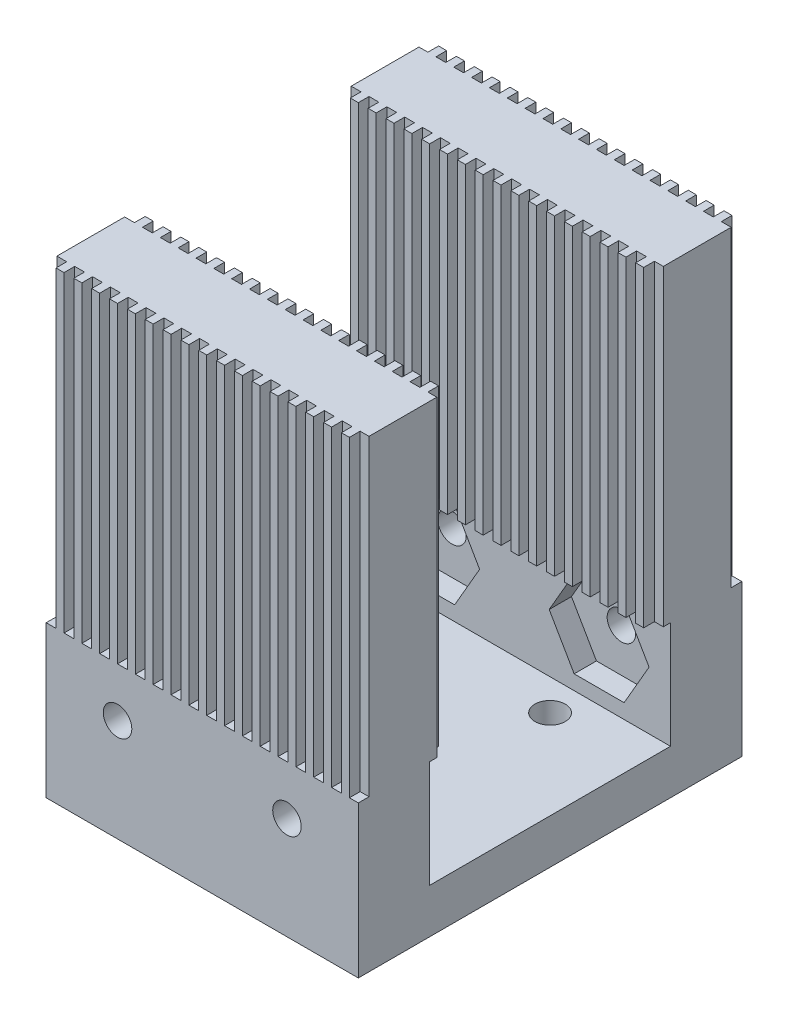
SolidWorks part; units mm, degrees
ref_plane "Front Plane" through (0, 0, 0) normal (0, 0, 1) x (1, 0, 0)
ref_plane "Top Plane" through (0, 0, 0) normal (0, 1, 0) x (1, 0, 0)
ref_plane "Right Plane" through (0, 0, 0) normal (1, 0, 0) x (0, 0, -1)
sketch "Sketch11" plane through (0, 0, 12.5) normal (0, -1, 0) x (1, 0, 0)
  line L1 (0, 0) -> (35, 0)
  line L2 (0, 0) -> (0, -27)
  line L3 (0, -27) -> (35, -27)
  line L4 (35, 0) -> (35, -27)
  dimension "D1" = 27
  dimension "D2" = 35
extrude "Boss-Extrude6" add sketch "Sketch11" along normal blind 5
sketch "Sketch12" plane through (0, -5, 0) normal (0, -1, 0) x (1, 0, 0)
  line L0 (0, 12.5) -> (0, -14.5) construction
  line L1 (0, -14.5) -> (35, -14.5) construction
  line L3 (35, 12.5) -> (0, 12.5) construction
  circle A0 centre (10, 9) radius 1.7
  circle A1 centre (25, 9) radius 1.7
  circle A2 centre (25, -11) radius 1.7
  circle A3 centre (10, -11) radius 1.7
  point P0 (17.5, -1)
  dimension "D3" = 3.4
  dimension "D4" = 7.5
  dimension "D1" = 17.5
  dimension "D2" = 13.5
  dimension "D5" = 10
  dimension "D7" = 27
  dimension "D6" = 2
extrude "Cut-Extrude3" cut sketch "Sketch12" against normal blind 5
sketch "Sketch13" plane through (0, -5, 0) normal (0, -1, 0) x (1, 0, 0)
  line L1 (35, -14.5) -> (0, -14.5)
  line L2 (35, -14.5) -> (35, -22.5)
  line L3 (35, -22.5) -> (0, -22.5)
  line L4 (0, -14.5) -> (0, -22.5)
  line L5 (35, 12.5) -> (0, 12.5)
  line L6 (35, 12.5) -> (35, 20.5)
  line L7 (35, 20.5) -> (0, 20.5)
  line L8 (0, 12.5) -> (0, 20.5)
  dimension "D1" = 8
  dimension "D2" = 8
extrude "Boss-Extrude7" add sketch "Sketch13" against normal blind 17
sketch "Sketch14" plane through (0, 12, 0) normal (0, 1, 0) x (1, 0, 0)
  line L0 (0, -12.5) -> (35, -12.5) construction
  line L1 (35, -20.5) -> (0, -20.5)
  line L2 (35, -20.5) -> (35, -10.5)
  line L3 (35, -10.5) -> (0, -10.5)
  line L4 (0, -20.5) -> (0, -10.5)
  line L5 (0, 22.5) -> (35, 22.5)
  line L6 (0, 22.5) -> (0, 12.5)
  line L7 (0, 12.5) -> (35, 12.5)
  line L8 (35, 22.5) -> (35, 12.5)
  line L9 (35, 14.5) -> (0, 14.5) construction
  dimension "D1" = 2
  dimension "D2" = 2
extrude "Boss-Extrude8" add sketch "Sketch14" along normal blind 35
sketch "Sketch15" plane through (0, 0, 10.5) normal (0, 0, -1) x (-1, 0, 0)
  line L0 (-35, 47) -> (0, 47) construction
  line L1 (0, 12) -> (-1.1, 12)
  line L2 (0, 12) -> (0, 47)
  line L3 (0, 47) -> (-1.1, 47)
  line L4 (-1.1, 12) -> (-1.1, 47)
  line L5 (-3.1, 12) -> (-3.1, 47)
  line L6 (-2, 47) -> (-3.1, 47)
  line L7 (-2, 12) -> (-2, 47)
  line L8 (-2, 12) -> (-3.1, 12)
  line L9 (-5.1, 12) -> (-5.1, 47)
  line L10 (-4, 47) -> (-5.1, 47)
  line L11 (-4, 12) -> (-4, 47)
  line L12 (-4, 12) -> (-5.1, 12)
  line L13 (-7.1, 12) -> (-7.1, 47)
  line L14 (-6, 47) -> (-7.1, 47)
  line L15 (-6, 12) -> (-6, 47)
  line L16 (-6, 12) -> (-7.1, 12)
  line L17 (-9.1, 12) -> (-9.1, 47)
  line L18 (-8, 47) -> (-9.1, 47)
  line L19 (-8, 12) -> (-8, 47)
  line L20 (-8, 12) -> (-9.1, 12)
  line L21 (-11.1, 12) -> (-11.1, 47)
  line L22 (-10, 47) -> (-11.1, 47)
  line L23 (-10, 12) -> (-10, 47)
  line L24 (-10, 12) -> (-11.1, 12)
  line L25 (-13.1, 12) -> (-13.1, 47)
  line L26 (-12, 47) -> (-13.1, 47)
  line L27 (-12, 12) -> (-12, 47)
  line L28 (-12, 12) -> (-13.1, 12)
  line L29 (-15.1, 12) -> (-15.1, 47)
  line L30 (-14, 47) -> (-15.1, 47)
  line L31 (-14, 12) -> (-14, 47)
  line L32 (-14, 12) -> (-15.1, 12)
  line L33 (-17.1, 12) -> (-17.1, 47)
  line L34 (-16, 47) -> (-17.1, 47)
  line L35 (-16, 12) -> (-16, 47)
  line L36 (-16, 12) -> (-17.1, 12)
  line L37 (-19.1, 12) -> (-19.1, 47)
  line L38 (-18, 47) -> (-19.1, 47)
  line L39 (-18, 12) -> (-18, 47)
  line L40 (-18, 12) -> (-19.1, 12)
  line L41 (-21.1, 12) -> (-21.1, 47)
  line L42 (-20, 47) -> (-21.1, 47)
  line L43 (-20, 12) -> (-20, 47)
  line L44 (-20, 12) -> (-21.1, 12)
  line L45 (-23.1, 12) -> (-23.1, 47)
  line L46 (-22, 47) -> (-23.1, 47)
  line L47 (-22, 12) -> (-22, 47)
  line L48 (-22, 12) -> (-23.1, 12)
  line L49 (-25.1, 12) -> (-25.1, 47)
  line L50 (-24, 47) -> (-25.1, 47)
  line L51 (-24, 12) -> (-24, 47)
  line L52 (-24, 12) -> (-25.1, 12)
  line L53 (-27.1, 12) -> (-27.1, 47)
  line L54 (-26, 47) -> (-27.1, 47)
  line L55 (-26, 12) -> (-26, 47)
  line L56 (-26, 12) -> (-27.1, 12)
  line L57 (-29.1, 12) -> (-29.1, 47)
  line L58 (-28, 47) -> (-29.1, 47)
  line L59 (-28, 12) -> (-28, 47)
  line L60 (-28, 12) -> (-29.1, 12)
  line L61 (-31.1, 12) -> (-31.1, 47)
  line L62 (-30, 47) -> (-31.1, 47)
  line L63 (-30, 12) -> (-30, 47)
  line L64 (-30, 12) -> (-31.1, 12)
  line L65 (-33.1, 12) -> (-33.1, 47)
  line L66 (-32, 47) -> (-33.1, 47)
  line L67 (-32, 12) -> (-32, 47)
  line L68 (-32, 12) -> (-33.1, 12)
  line L69 (-35.1, 12) -> (-35.1, 47)
  line L70 (-34, 47) -> (-35.1, 47)
  line L71 (-34, 12) -> (-34, 47)
  line L72 (-34, 12) -> (-35.1, 12)
  dimension "D1" = 1.1
  dimension "D2" = 18
extrude "Cut-Extrude4" cut sketch "Sketch15" against normal blind 1.2
sketch "Sketch16" plane through (0, 0, -12.5) normal (0, 0, 1) x (1, 0, 0)
  line L0 (0, 12) -> (35, 12) construction
  line L1 (0, 47) -> (1.1, 47)
  line L2 (0, 47) -> (0, 12)
  line L3 (0, 12) -> (1.1, 12)
  line L4 (1.1, 47) -> (1.1, 12)
  line L5 (2, 47) -> (2, 12)
  line L6 (2, 12) -> (3.1, 12)
  line L7 (3.1, 47) -> (3.1, 12)
  line L8 (2, 47) -> (3.1, 47)
  line L9 (4, 47) -> (4, 12)
  line L10 (4, 12) -> (5.1, 12)
  line L11 (5.1, 47) -> (5.1, 12)
  line L12 (4, 47) -> (5.1, 47)
  line L13 (6, 47) -> (6, 12)
  line L14 (6, 12) -> (7.1, 12)
  line L15 (7.1, 47) -> (7.1, 12)
  line L16 (6, 47) -> (7.1, 47)
  line L17 (8, 47) -> (8, 12)
  line L18 (8, 12) -> (9.1, 12)
  line L19 (9.1, 47) -> (9.1, 12)
  line L20 (8, 47) -> (9.1, 47)
  line L21 (10, 47) -> (10, 12)
  line L22 (10, 12) -> (11.1, 12)
  line L23 (11.1, 47) -> (11.1, 12)
  line L24 (10, 47) -> (11.1, 47)
  line L25 (12, 47) -> (12, 12)
  line L26 (12, 12) -> (13.1, 12)
  line L27 (13.1, 47) -> (13.1, 12)
  line L28 (12, 47) -> (13.1, 47)
  line L29 (14, 47) -> (14, 12)
  line L30 (14, 12) -> (15.1, 12)
  line L31 (15.1, 47) -> (15.1, 12)
  line L32 (14, 47) -> (15.1, 47)
  line L33 (16, 47) -> (16, 12)
  line L34 (16, 12) -> (17.1, 12)
  line L35 (17.1, 47) -> (17.1, 12)
  line L36 (16, 47) -> (17.1, 47)
  line L37 (18, 47) -> (18, 12)
  line L38 (18, 12) -> (19.1, 12)
  line L39 (19.1, 47) -> (19.1, 12)
  line L40 (18, 47) -> (19.1, 47)
  line L41 (20, 47) -> (20, 12)
  line L42 (20, 12) -> (21.1, 12)
  line L43 (21.1, 47) -> (21.1, 12)
  line L44 (20, 47) -> (21.1, 47)
  line L45 (22, 47) -> (22, 12)
  line L46 (22, 12) -> (23.1, 12)
  line L47 (23.1, 47) -> (23.1, 12)
  line L48 (22, 47) -> (23.1, 47)
  line L49 (24, 47) -> (24, 12)
  line L50 (24, 12) -> (25.1, 12)
  line L51 (25.1, 47) -> (25.1, 12)
  line L52 (24, 47) -> (25.1, 47)
  line L53 (26, 47) -> (26, 12)
  line L54 (26, 12) -> (27.1, 12)
  line L55 (27.1, 47) -> (27.1, 12)
  line L56 (26, 47) -> (27.1, 47)
  line L57 (28, 47) -> (28, 12)
  line L58 (28, 12) -> (29.1, 12)
  line L59 (29.1, 47) -> (29.1, 12)
  line L60 (28, 47) -> (29.1, 47)
  line L61 (30, 47) -> (30, 12)
  line L62 (30, 12) -> (31.1, 12)
  line L63 (31.1, 47) -> (31.1, 12)
  line L64 (30, 47) -> (31.1, 47)
  line L65 (32, 47) -> (32, 12)
  line L66 (32, 12) -> (33.1, 12)
  line L67 (33.1, 47) -> (33.1, 12)
  line L68 (32, 47) -> (33.1, 47)
  line L69 (34, 47) -> (34, 12)
  line L70 (34, 12) -> (35.1, 12)
  line L71 (35.1, 47) -> (35.1, 12)
  line L72 (34, 47) -> (35.1, 47)
  dimension "D1" = 1.1
  dimension "D2" = 18
extrude "Cut-Extrude5" cut sketch "Sketch16" against normal blind 1.2
sketch "Sketch17" plane through (0, 0, 20.5) normal (0, 0, 1) x (1, 0, 0)
  line L0 (2, 47) -> (2, 12)
  line L1 (0, 47) -> (1.1, 47)
  line L2 (0, 47) -> (0, 12)
  line L3 (0, 12) -> (1.1, 12)
  line L4 (1.1, 47) -> (1.1, 12)
  line L5 (2, 47) -> (3.1, 47)
  line L6 (3.1, 47) -> (3.1, 12)
  line L7 (2, 12) -> (3.1, 12)
  line L8 (4, 47) -> (4, 12)
  line L9 (4, 47) -> (5.1, 47)
  line L10 (5.1, 47) -> (5.1, 12)
  line L11 (4, 12) -> (5.1, 12)
  line L12 (6, 47) -> (6, 12)
  line L13 (6, 47) -> (7.1, 47)
  line L14 (7.1, 47) -> (7.1, 12)
  line L15 (6, 12) -> (7.1, 12)
  line L16 (8, 47) -> (8, 12)
  line L17 (8, 47) -> (9.1, 47)
  line L18 (9.1, 47) -> (9.1, 12)
  line L19 (8, 12) -> (9.1, 12)
  line L20 (10, 47) -> (10, 12)
  line L21 (10, 47) -> (11.1, 47)
  line L22 (11.1, 47) -> (11.1, 12)
  line L23 (10, 12) -> (11.1, 12)
  line L24 (12, 47) -> (12, 12)
  line L25 (12, 47) -> (13.1, 47)
  line L26 (13.1, 47) -> (13.1, 12)
  line L27 (12, 12) -> (13.1, 12)
  line L28 (14, 47) -> (14, 12)
  line L29 (14, 47) -> (15.1, 47)
  line L30 (15.1, 47) -> (15.1, 12)
  line L31 (14, 12) -> (15.1, 12)
  line L32 (16, 47) -> (16, 12)
  line L33 (16, 47) -> (17.1, 47)
  line L34 (17.1, 47) -> (17.1, 12)
  line L35 (16, 12) -> (17.1, 12)
  line L36 (18, 47) -> (18, 12)
  line L37 (18, 47) -> (19.1, 47)
  line L38 (19.1, 47) -> (19.1, 12)
  line L39 (18, 12) -> (19.1, 12)
  line L40 (20, 47) -> (20, 12)
  line L41 (20, 47) -> (21.1, 47)
  line L42 (21.1, 47) -> (21.1, 12)
  line L43 (20, 12) -> (21.1, 12)
  line L44 (22, 47) -> (22, 12)
  line L45 (22, 47) -> (23.1, 47)
  line L46 (23.1, 47) -> (23.1, 12)
  line L47 (22, 12) -> (23.1, 12)
  line L48 (24, 47) -> (24, 12)
  line L49 (24, 47) -> (25.1, 47)
  line L50 (25.1, 47) -> (25.1, 12)
  line L51 (24, 12) -> (25.1, 12)
  line L52 (26, 47) -> (26, 12)
  line L53 (26, 47) -> (27.1, 47)
  line L54 (27.1, 47) -> (27.1, 12)
  line L55 (26, 12) -> (27.1, 12)
  line L56 (28, 47) -> (28, 12)
  line L57 (28, 47) -> (29.1, 47)
  line L58 (29.1, 47) -> (29.1, 12)
  line L59 (28, 12) -> (29.1, 12)
  line L60 (30, 47) -> (30, 12)
  line L61 (30, 47) -> (31.1, 47)
  line L62 (31.1, 47) -> (31.1, 12)
  line L63 (30, 12) -> (31.1, 12)
  line L64 (32, 47) -> (32, 12)
  line L65 (32, 47) -> (33.1, 47)
  line L66 (33.1, 47) -> (33.1, 12)
  line L67 (32, 12) -> (33.1, 12)
  line L68 (34, 47) -> (34, 12)
  line L69 (34, 47) -> (35.1, 47)
  line L70 (35.1, 47) -> (35.1, 12)
  line L71 (34, 12) -> (35.1, 12)
  dimension "D1" = 1.1
  dimension "D2" = 35
  dimension "D3" = 18
extrude "Cut-Extrude6" cut sketch "Sketch17" against normal blind 1.2
sketch "Sketch18" plane through (0, 0, -22.5) normal (0, 0, -1) x (-1, 0, 0)
  line L0 (-31.9, 47) -> (-31.9, 12)
  line L1 (-35, 47) -> (-33.9, 47)
  line L2 (-35, 47) -> (-35, 12)
  line L3 (-35, 12) -> (-33.9, 12)
  line L4 (-33.9, 47) -> (-33.9, 12)
  line L5 (-33, 12) -> (-31.9, 12)
  line L6 (-33, 47) -> (-33, 12)
  line L7 (-33, 47) -> (-31.9, 47)
  line L8 (-29.9, 47) -> (-29.9, 12)
  line L9 (-31, 12) -> (-29.9, 12)
  line L10 (-31, 47) -> (-31, 12)
  line L11 (-31, 47) -> (-29.9, 47)
  line L12 (-27.9, 47) -> (-27.9, 12)
  line L13 (-29, 12) -> (-27.9, 12)
  line L14 (-29, 47) -> (-29, 12)
  line L15 (-29, 47) -> (-27.9, 47)
  line L16 (-25.9, 47) -> (-25.9, 12)
  line L17 (-27, 12) -> (-25.9, 12)
  line L18 (-27, 47) -> (-27, 12)
  line L19 (-27, 47) -> (-25.9, 47)
  line L20 (-23.9, 47) -> (-23.9, 12)
  line L21 (-25, 12) -> (-23.9, 12)
  line L22 (-25, 47) -> (-25, 12)
  line L23 (-25, 47) -> (-23.9, 47)
  line L24 (-21.9, 47) -> (-21.9, 12)
  line L25 (-23, 12) -> (-21.9, 12)
  line L26 (-23, 47) -> (-23, 12)
  line L27 (-23, 47) -> (-21.9, 47)
  line L28 (-19.9, 47) -> (-19.9, 12)
  line L29 (-21, 12) -> (-19.9, 12)
  line L30 (-21, 47) -> (-21, 12)
  line L31 (-21, 47) -> (-19.9, 47)
  line L32 (-17.9, 47) -> (-17.9, 12)
  line L33 (-19, 12) -> (-17.9, 12)
  line L34 (-19, 47) -> (-19, 12)
  line L35 (-19, 47) -> (-17.9, 47)
  line L36 (-15.9, 47) -> (-15.9, 12)
  line L37 (-17, 12) -> (-15.9, 12)
  line L38 (-17, 47) -> (-17, 12)
  line L39 (-17, 47) -> (-15.9, 47)
  line L40 (-13.9, 47) -> (-13.9, 12)
  line L41 (-15, 12) -> (-13.9, 12)
  line L42 (-15, 47) -> (-15, 12)
  line L43 (-15, 47) -> (-13.9, 47)
  line L44 (-11.9, 47) -> (-11.9, 12)
  line L45 (-13, 12) -> (-11.9, 12)
  line L46 (-13, 47) -> (-13, 12)
  line L47 (-13, 47) -> (-11.9, 47)
  line L48 (-9.9, 47) -> (-9.9, 12)
  line L49 (-11, 12) -> (-9.9, 12)
  line L50 (-11, 47) -> (-11, 12)
  line L51 (-11, 47) -> (-9.9, 47)
  line L52 (-7.9, 47) -> (-7.9, 12)
  line L53 (-9, 12) -> (-7.9, 12)
  line L54 (-9, 47) -> (-9, 12)
  line L55 (-9, 47) -> (-7.9, 47)
  line L56 (-5.9, 47) -> (-5.9, 12)
  line L57 (-7, 12) -> (-5.9, 12)
  line L58 (-7, 47) -> (-7, 12)
  line L59 (-7, 47) -> (-5.9, 47)
  line L60 (-3.9, 47) -> (-3.9, 12)
  line L61 (-5, 12) -> (-3.9, 12)
  line L62 (-5, 47) -> (-5, 12)
  line L63 (-5, 47) -> (-3.9, 47)
  line L64 (-1.9, 47) -> (-1.9, 12)
  line L65 (-3, 12) -> (-1.9, 12)
  line L66 (-3, 47) -> (-3, 12)
  line L67 (-3, 47) -> (-1.9, 47)
  line L68 (0.1, 47) -> (0.1, 12)
  line L69 (-1, 12) -> (0.1, 12)
  line L70 (-1, 47) -> (-1, 12)
  line L71 (-1, 47) -> (0.1, 47)
  dimension "D1" = 1.1
  dimension "D2" = 35
  dimension "D3" = 18
extrude "Cut-Extrude7" cut sketch "Sketch18" against normal blind 1.2
sketch "Sketch19" plane through (0, 0, -22.5) normal (0, 0, -1) x (-1, 0, 0)
  line L0 (-35, 12) -> (-35, -5) construction
  line L1 (0, 12) -> (0, -5) construction
  circle A0 centre (-27, 6.4851) radius 1.6
  circle A1 centre (-8, 6.4851) radius 1.6
  dimension "D1" = 8
  dimension "D2" = 8
extrude "Cut-Extrude8" cut sketch "Sketch19" against normal through all
sketch "Sketch20" plane through (0, 0, -14.5) normal (0, 0, 1) x (1, 0, 0)
  line L1 (29.8, 1.6354) -> (32.6, 6.4851)
  line L2 (32.6, 6.4851) -> (29.8, 11.3348)
  line L3 (29.8, 11.3348) -> (24.2, 11.3348)
  line L4 (24.2, 11.3348) -> (21.4, 6.4851)
  line L5 (21.4, 6.4851) -> (24.2, 1.6354)
  line L6 (24.2, 1.6354) -> (29.8, 1.6354)
  line L7 (10.8, 1.6354) -> (13.6, 6.4851)
  line L8 (13.6, 6.4851) -> (10.8, 11.3348)
  line L9 (10.8, 11.3348) -> (5.2, 11.3348)
  line L10 (5.2, 11.3348) -> (2.4, 6.4851)
  line L11 (2.4, 6.4851) -> (5.2, 1.6354)
  line L12 (5.2, 1.6354) -> (10.8, 1.6354)
  circle A0 centre (27, 6.4851) radius 4.8497 construction
  circle A1 centre (8, 6.4851) radius 4.8497 construction
  dimension "D1" = 5.6
  dimension "D2" = 5.6
extrude "Cut-Extrude9" cut sketch "Sketch20" against normal blind 2.5
sketch "Sketch21" plane through (0, 0, 12.5) normal (0, 0, -1) x (-1, 0, 0)
  line L1 (-5.2, 1.6354) -> (-2.4, 6.4851)
  line L2 (-2.4, 6.4851) -> (-5.2, 11.3348)
  line L3 (-5.2, 11.3348) -> (-10.8, 11.3348)
  line L4 (-10.8, 11.3348) -> (-13.6, 6.4851)
  line L5 (-13.6, 6.4851) -> (-10.8, 1.6354)
  line L6 (-10.8, 1.6354) -> (-5.2, 1.6354)
  line L7 (-24.2, 1.6354) -> (-21.4, 6.4851)
  line L8 (-21.4, 6.4851) -> (-24.2, 11.3348)
  line L9 (-24.2, 11.3348) -> (-29.8, 11.3348)
  line L10 (-29.8, 11.3348) -> (-32.6, 6.4851)
  line L11 (-32.6, 6.4851) -> (-29.8, 1.6354)
  line L12 (-29.8, 1.6354) -> (-24.2, 1.6354)
  circle A0 centre (-8, 6.4851) radius 4.8497 construction
  circle A1 centre (-27, 6.4851) radius 4.8497 construction
  dimension "D1" = 5.6
  dimension "D2" = 5.6
extrude "Cut-Extrude10" cut sketch "Sketch21" against normal blind 2.5
